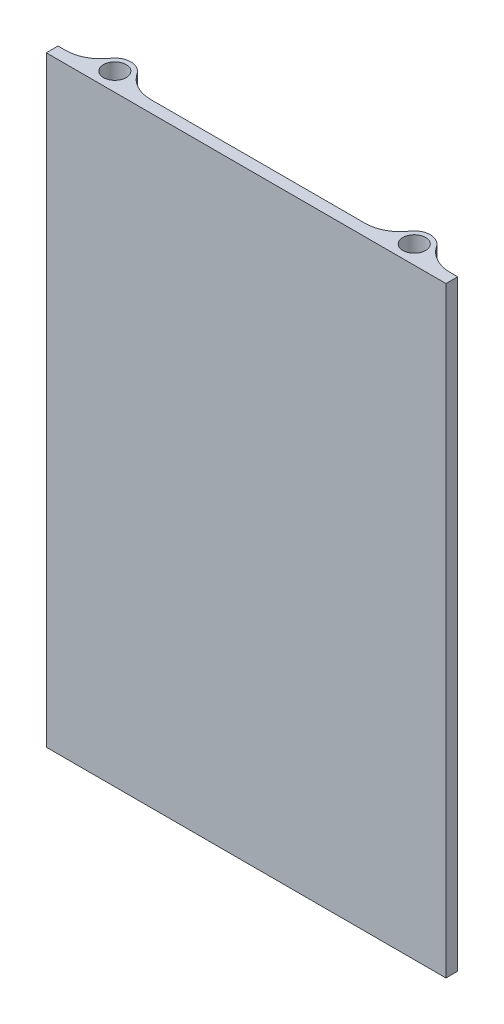
SolidWorks part; units mm, degrees
material "PLA"
ref_plane "Front Plane" through (0, 0, 0) normal (0, 0, 1) x (1, 0, 0)
ref_plane "Top Plane" through (0, 0, 0) normal (0, 1, 0) x (1, 0, 0)
ref_plane "Right Plane" through (0, 0, 0) normal (1, 0, 0) x (0, 0, -1)
other "Center of Mass"
sketch "Sketch1" plane through (0, 0, 0) normal (0, 1, 0) x (1, 0, 0)
  line L19 (85, -5) -> (85, 0)
  line L20 (85, -5) -> (-85, -5)
  line L24 (85, 0) -> (81.7969, 0)
  line L25 (-85, -5) -> (-85, 0)
  line L26 (85, -5) -> (-85, 0) construction
  line L27 (85, 0) -> (-85, -5) construction
  line L28 (0, 0) -> (0, -5) construction
  line L29 (-81.7969, 0) -> (-85, 0)
  line L30 (45.5631, 0) -> (-45.5631, 0)
  circle A29 centre (-63.68, 2.83) radius 4.825
  arc A30 (-69.8906, 0) -> (-57.4694, 0) centre (-63.68, 2.83) ccw construction
  arc A31 (-81.7969, 0) -> (-69.3454, 6.6357) centre (-81.7969, 15) ccw
  arc A32 (-58.0146, 6.6357) -> (-45.5631, 0) centre (-45.5631, 15) ccw
  arc A33 (-58.0146, 6.6357) -> (-69.3454, 6.6357) centre (-63.68, 2.83) ccw
  arc A34 (69.8906, 0) -> (57.4694, 0) centre (63.68, 2.83) cw construction
  arc A35 (58.0146, 6.6357) -> (69.3454, 6.6357) centre (63.68, 2.83) cw
  arc A36 (58.0146, 6.6357) -> (45.5631, 0) centre (45.5631, 15) cw
  arc A37 (81.7969, 0) -> (69.3454, 6.6357) centre (81.7969, 15) cw
  circle A38 centre (63.68, 2.83) radius 4.825
  point P1 (0, -2.5)
  dimension "D3" = 9.65
  dimension "D4" = 7.83
  dimension "D5" = 63.68
  dimension "D6" = 13.65
  dimension "D1" = 5
  dimension "D2" = 170
extrude "Boss-Extrude1" add sketch "Sketch1" along normal blind 255.8
equation "\"rod_d\"= 9.65"
equation "\"big_bearing_id\"= 140mm"
equation "\"rod_offset_c2c\"= \"big_bearing_id\" / 2 - \"rod_d\" / 2 - 1.5"
